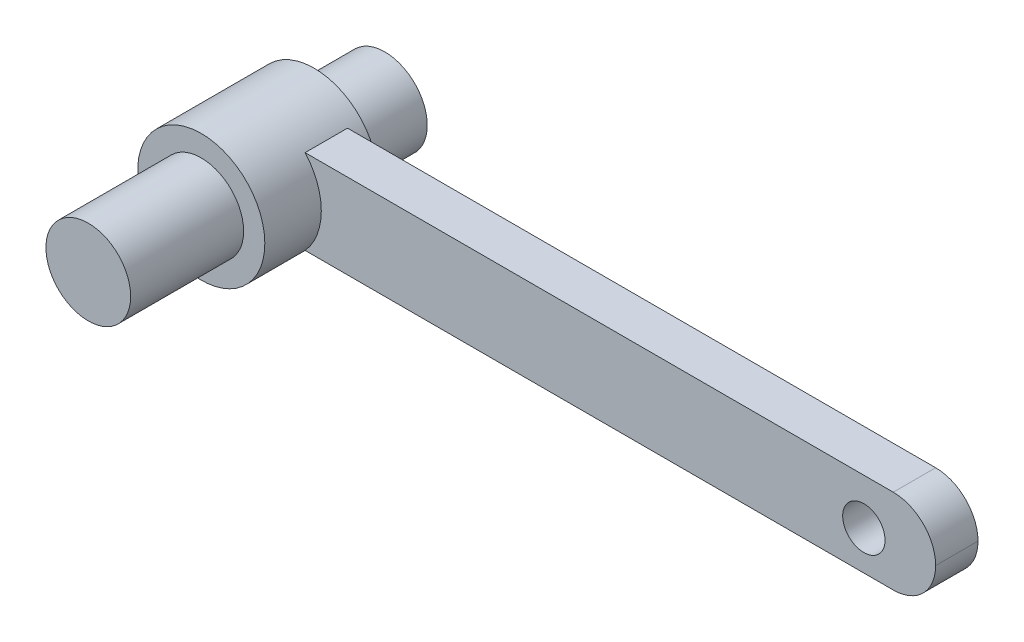
SolidWorks part; units mm, degrees
ref_plane "前视基准面" through (0, 0, 0) normal (0, 0, 1) x (1, 0, 0)
ref_plane "上视基准面" through (0, 0, 0) normal (0, 1, 0) x (1, 0, 0)
ref_plane "右视基准面" through (0, 0, 0) normal (1, 0, 0) x (0, 0, -1)
sketch "草图1" plane through (0, 0, 0) normal (0, 0, 1) x (1, 0, 0)
  circle A0 centre (-10.5, -0.5) radius 0.3
  circle A1 centre (-10.5, -0.5) radius 0.45
extrude "凸台-拉伸1" add sketch "草图1" along normal blind 0.8
sketch "草图2" plane through (0, 0, 0.8) normal (0, 0, 1) x (1, 0, 0)
  line L0 (-10.5, -0.5) -> (-10.2, -0.5)
  circle A0 centre (-10.5, -0.5) radius 0.3 construction
ref_plane "基准面1" through (-10.2, -0.5, 0.8) normal (1, 0, 0) x (0, 0, -1)
sketch "草图3" plane through (-10.2, -0.5, 0.8) normal (1, 0, 0) x (0, 0, -1)
  line L1 (0.4, -0.3) -> (0.4, 0.3)
  line L2 (0.4, 0.3) -> (0.7, 0.3)
  line L3 (0.7, 0.3) -> (0.7, -0.3)
  line L4 (0.7, -0.3) -> (0.4, -0.3)
  arc A0 (0.7, 0) -> (0.6583, 0.1527) centre (0.4, 0) ccw
  dimension "D2" = 0.6
extrude "凸台-拉伸4" add sketch "草图3" along normal blind 4.5 contours L4 L3 L2 L1 region at (-10.2, -0.5, 0.25)
sketch "草图7" plane through (0, 0, 0.4) normal (0, 0, 1) x (1, 0, 0)
  circle A0 centre (-6.2082, -0.5243) radius 0.15
  dimension "D1" = 0.3
extrude "切除-拉伸3" cut sketch "草图7" against normal blind 4.5
fillet "圆角1" radius 0.3 2 edges at (-5.7, -0.8, 0.25) (-5.7, -0.2, 0.25)
sketch "草图8" plane through (0, 0, 0.8) normal (0, 0, 1) x (1, 0, 0)
  circle A0 centre (-10.5, -0.5) radius 0.3
extrude "凸台-拉伸5" add sketch "草图8" along normal blind 0.8 and the other way blind 1.3
